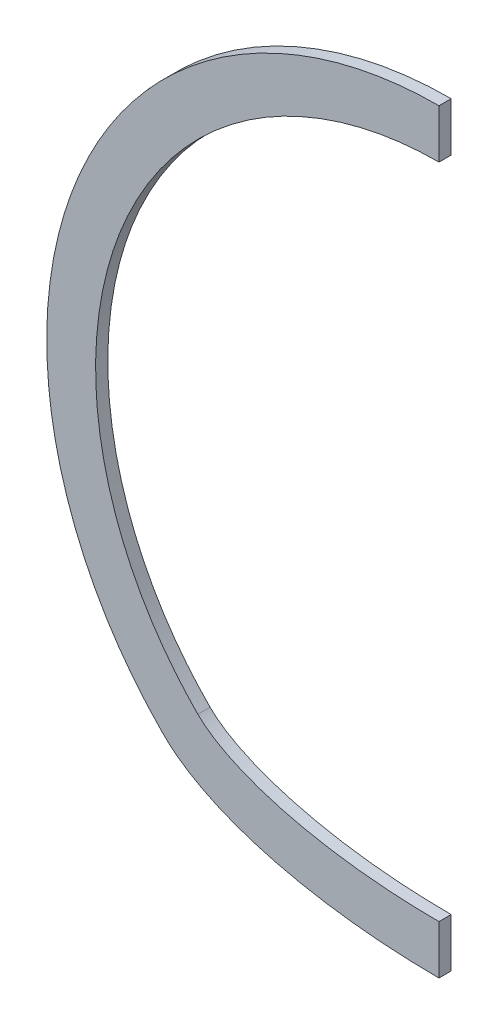
SolidWorks part; units mm, degrees
material "Balsa"
ref_plane "Front Plane" through (0, 0, 0) normal (0, 0, 1) x (1, 0, 0)
ref_plane "Top Plane" through (0, 0, 0) normal (0, 1, 0) x (1, 0, 0)
ref_plane "Right Plane" through (0, 0, 0) normal (1, 0, 0) x (0, 0, -1)
sketch "Sketch2" plane through (0, 0, 0) normal (0, 0, 1) x (1, 0, 0)
  spline S0 degree 3 poles (2568.0953, -4090.4659) (-4057.024, 3451.1389) (4945.1528, -1980.2124) (-4825.8731, 402.3844) knots -545.10296 -545.10296 -545.10296 -545.10296 547.49362 547.49362 547.49362 547.49362 only from (49.5009, 91.348) to (50.6103, 90.7129)
  spline S1 degree 3 poles (3341.4723, -3725.6669) (-100.6677, -22.1088) (-50.1916, -95.8099) (-74.4696, -70.0026) (-75.8372, -68.488) (-77.1861, -66.9319) (-78.5157, -65.3347) (-79.8244, -63.6962) (-81.5476, -61.4464) (-83.6416, -58.5297) (-85.6296, -55.5014) (-87.1622, -52.9973) (-88.2859, -51.0701) (-90.1147, -47.7724) (-92.5499, -42.8914) (-95.3516, -36.1752) (-97.8068, -28.8548) (-99.4166, -22.4927) (-100.4844, -16.9735) (-101.2174, -12.1158) (-101.8059, -6.1085) (-102.0556, 1.0556) (-101.6376, 11.9166) (-99.5817, 24.7034) (-94.9478, 39.4776) (-88.6565, 52.7081) (-80.0434, 65.5541) (-69.8712, 76.7554) (-58.637, 85.9148) (-47.202, 92.899) (-35.7905, 98.0522) (-24.0008, 101.7167) (-12.0295, 103.8942) (-3.6569, 104.3953) (0.9911, 104.3723) (2.6447, 104.3478) (5.2959, 104.2559) (8.9441, 104.0024) (12.9235, 103.5662) (16.8979, 102.9692) (20.8607, 102.2106) (24.805, 101.2899) (28.7242, 100.207) (32.6113, 98.9619) (36.4593, 97.5551) (39.9429, 96.1186) (42.4433, 94.9816) (43.9946, 94.2376) (44.9225, 93.7809) (45.8466, 93.3143) (46.7667, 92.8378) (47.6827, 92.3514) (70.4007, 80.003) (151.5153, 23.3747) (-4363.3748, 2440.7113) knots -0.313173 -0.313173 -0.313173 -0.313173 0.006795 0.013654 0.020575 0.02756 0.034609 0.041722 0.048899 0.063446 0.078252 0.085753 0.09332 0.100952 0.124124 0.148785 0.174948 0.202627 0.215494 0.232144 0.2526 0.276886 0.305032 0.363116 0.408011 0.462235 0.511576 0.564908 0.615598 0.658549 0.700916 0.742691 0.78387 0.82445 0.827809 0.831171 0.841279 0.854802 0.868378 0.882008 0.895692 0.909428 0.923217 0.93706 0.950955 0.964902 0.975398 0.978902 0.982411 0.985922 0.989437 0.992954 0.996476 1.262403 1.262403 1.262403 1.262403 only from (-71.6774, -72.9104) to (49.5009, 91.348)
  spline S2 degree 3 poles (-71.6774, -72.9104) (-72.1092, -72.4767) (-72.9729, -71.5936) (-74.4696, -70.0026) (-75.8372, -68.488) (-77.1861, -66.9319) (-78.5157, -65.3347) (-79.8244, -63.6962) (-81.5476, -61.4464) (-83.6416, -58.5297) (-85.6296, -55.5014) (-87.1622, -52.9973) (-88.2859, -51.0701) (-90.1147, -47.7724) (-92.5499, -42.8914) (-95.3516, -36.1752) (-97.8068, -28.8548) (-99.4166, -22.4927) (-100.4844, -16.9735) (-101.2174, -12.1158) (-101.8059, -6.1085) (-102.0556, 1.0556) (-101.6376, 11.9166) (-99.5817, 24.7034) (-94.9478, 39.4776) (-88.6565, 52.7081) (-80.0434, 65.5541) (-69.8712, 76.7554) (-58.637, 85.9148) (-47.202, 92.899) (-35.7905, 98.0522) (-24.0008, 101.7167) (-12.0295, 103.8942) (-3.6569, 104.3953) (0.9911, 104.3723) (2.6447, 104.3478) (5.2959, 104.2559) (8.9441, 104.0024) (12.9235, 103.5662) (16.8979, 102.9692) (20.8607, 102.2106) (24.805, 101.2899) (28.7242, 100.207) (32.6113, 98.9619) (36.4593, 97.5551) (39.9429, 96.1186) (42.4433, 94.9816) (43.9946, 94.2376) (44.9225, 93.7809) (45.8466, 93.3143) (46.7667, 92.8378) (47.6827, 92.3514) (48.5618, 91.8735) (49.1883, 91.5244) (49.5009, 91.348) knots 0 0 0 0 0.006795 0.013654 0.020575 0.02756 0.034609 0.041722 0.048899 0.063446 0.078252 0.085753 0.09332 0.100952 0.124124 0.148785 0.174948 0.202627 0.215494 0.232144 0.2526 0.276886 0.305032 0.363116 0.408011 0.462235 0.511576 0.564908 0.615598 0.658549 0.700916 0.742691 0.78387 0.82445 0.827809 0.831171 0.841279 0.854802 0.868378 0.882008 0.895692 0.909428 0.923217 0.93706 0.950955 0.964902 0.975398 0.978902 0.982411 0.985922 0.989437 0.992954 0.996476 1 1 1 1
  spline S3 degree 3 poles (49.5009, 91.348) (49.872, 91.1385) (50.2418, 90.9268) (50.6103, 90.7129) knots 0 0 0 0 1 1 1 1
  spline S4 degree 3 poles (-4193.7763, 2732.8048) (81.5381, 53.7028) (23.1515, 107.7521) (53.9325, 88.7036) (55.5798, 87.6387) (57.2181, 86.5331) (58.847, 85.3874) (60.4652, 84.2011) (62.6149, 82.559) (65.2687, 80.4032) (68.3802, 77.661) (71.4204, 74.7537) (74.3792, 71.6812) (77.2464, 68.4441) (79.5428, 65.6199) (81.3243, 63.2803) (82.6352, 61.4798) (83.9151, 59.6395) (85.6826, 56.9767) (87.8969, 53.3695) (90.4626, 48.6769) (92.8892, 43.6261) (95.1327, 38.2157) (97.1465, 32.4482) (98.8821, 26.3306) (100.2892, 19.8751) (101.2586, 13.4739) (101.8173, 7.2467) (102.0152, 1.305) (101.8786, -4.6242) (101.3926, -10.7347) (100.5371, -16.8676) (99.3294, -22.8638) (97.8936, -28.3722) (96.657, -32.2698) (95.7856, -34.7444) (95.046, -36.7643) (93.9532, -39.5358) (92.4358, -43.007) (90.8217, -46.3649) (89.1186, -49.6082) (87.3342, -52.7363) (85.4757, -55.7486) (83.5505, -58.6453) (81.5655, -61.4266) (79.3077, -64.3807) (77.437, -66.6472) (76.0073, -68.2889) (75.2951, -69.0897) (74.579, -69.8782) (73.8594, -70.6545) (73.1363, -71.4184) (59.0939, -85.9325) (120.7935, -16.6257) (-3396.6628, -3673.2191) knots -0.504739 -0.504739 -0.504739 -0.504739 0.010157 0.020393 0.030709 0.041103 0.051576 0.062128 0.072758 0.094254 0.116062 0.138181 0.16061 0.183347 0.206391 0.218027 0.22974 0.241529 0.253393 0.280162 0.30828 0.337739 0.36853 0.400644 0.434071 0.4688 0.504821 0.536145 0.567394 0.59857 0.62967 0.664059 0.696204 0.726123 0.75383 0.760691 0.767516 0.787768 0.807688 0.827278 0.84654 0.865477 0.884089 0.902378 0.920346 0.937994 0.961032 0.966703 0.97234 0.977942 0.983508 0.98904 0.994538 1.266327 1.266327 1.266327 1.266327 only from (50.6103, 90.7129) to (71.6784, -72.9104)
  spline S5 degree 3 poles (50.6103, 90.7129) (51.1284, 90.4118) (52.1672, 89.796) (53.9325, 88.7036) (55.5798, 87.6387) (57.2181, 86.5331) (58.847, 85.3874) (60.4652, 84.2011) (62.6149, 82.559) (65.2687, 80.4032) (68.3802, 77.661) (71.4204, 74.7537) (74.3792, 71.6812) (77.2464, 68.4441) (79.5428, 65.6199) (81.3243, 63.2803) (82.6352, 61.4798) (83.9151, 59.6395) (85.6826, 56.9767) (87.8969, 53.3695) (90.4626, 48.6769) (92.8892, 43.6261) (95.1327, 38.2157) (97.1465, 32.4482) (98.8821, 26.3306) (100.2892, 19.8751) (101.2586, 13.4739) (101.8173, 7.2467) (102.0152, 1.305) (101.8786, -4.6242) (101.3926, -10.7347) (100.5371, -16.8676) (99.3294, -22.8638) (97.8936, -28.3722) (96.657, -32.2698) (95.7856, -34.7444) (95.046, -36.7643) (93.9532, -39.5358) (92.4358, -43.007) (90.8217, -46.3649) (89.1186, -49.6082) (87.3342, -52.7363) (85.4757, -55.7486) (83.5505, -58.6453) (81.5655, -61.4266) (79.3077, -64.3807) (77.437, -66.6472) (76.0073, -68.2889) (75.2951, -69.0897) (74.579, -69.8782) (73.8594, -70.6545) (73.1363, -71.4184) (72.3175, -72.2647) (71.8912, -72.6967) (71.6784, -72.9104) knots 0 0 0 0 0.010157 0.020393 0.030709 0.041103 0.051576 0.062128 0.072758 0.094254 0.116062 0.138181 0.16061 0.183347 0.206391 0.218027 0.22974 0.241529 0.253393 0.280162 0.30828 0.337739 0.36853 0.400644 0.434071 0.4688 0.504821 0.536145 0.567394 0.59857 0.62967 0.664059 0.696204 0.726123 0.75383 0.760691 0.767516 0.787768 0.807688 0.827278 0.84654 0.865477 0.884089 0.902378 0.920346 0.937994 0.961032 0.966703 0.97234 0.977942 0.983508 0.98904 0.994538 1 1 1 1
  spline S6 degree 3 poles (-4835.9061, 806.008) (5645.7753, -391.3089) (-5645.7177, -391.3145) (4835.7602, 805.9912) knots -2.930767 -2.930767 -2.930767 -2.930767 3.930735 3.930735 3.930735 3.930735 weights 1 1 1 1 only from (71.6784, -72.9104) to (-71.6774, -72.9104)
  spline S7 degree 3 poles (71.6784, -72.9104) (46.3599, -98.3417) (-46.3589, -98.3417) (-71.6774, -72.9104) knots 0 0 0 0 1 1 1 1 weights 1 1 1 1
  spline S8 degree 1 poles (-62.6772, -63.9502) (43.2582, 80.2883) knots 0 0 1 1 construction
  spline S9 degree 1 poles (43.2582, 80.2883) (44.2327, 79.7303) knots 0 0 1 1 construction
  spline S10 degree 1 poles (44.2327, 79.7303) (62.6782, -63.9502) knots 0 0 1 1 construction
  spline S11 degree 1 poles (62.6782, -63.9502) (-62.6772, -63.9502) knots 0 0 1 1 construction
  spline S12 degree 3 poles (-62.6772, -63.9502) (-62.8955, -63.7309) (-63.3217, -63.2983) (-64.0021, -62.5921) (-64.7538, -61.7946) (-65.7039, -60.7646) (-66.8046, -59.5274) (-68.5568, -57.4681) (-70.6482, -54.8355) (-73.8114, -50.469) (-77.3945, -44.7561) (-82.3029, -35.1354) (-86.8108, -22.36) (-90.3543, -0.9674) (-87.6499, 26.3501) (-73.3334, 55.9721) (-49.624, 78.7088) (-24.4872, 89.3835) (-3.091, 92.1159) (13.039, 91.1975) (26.1203, 87.9966) (34.8794, 84.5248) (39.1021, 82.5104) (41.2143, 81.4108) (42.347, 80.7976) (42.9592, 80.4569) (43.2582, 80.2883) knots 0 0 0 0 0.003906 0.007812 0.011719 0.015625 0.023437 0.03125 0.046875 0.062499 0.093749 0.124999 0.187498 0.249998 0.374997 0.499996 0.624995 0.749994 0.812493 0.874993 0.937492 0.968742 0.984367 0.992179 0.996085 0.999992 0.999992 0.999992 0.999992
  spline S13 degree 3 poles (43.2582, 80.2883) (43.3397, 80.2423) (43.5025, 80.15) (43.7464, 80.0108) (43.9898, 79.871) (44.1518, 79.7773) (44.2327, 79.7303) knots 0.002022 0.002022 0.002022 0.002022 0.251014 0.500005 0.748996 0.997987 0.997987 0.997987 0.997987
  spline S14 degree 3 poles (44.2327, 79.7303) (44.5844, 79.526) (45.2596, 79.1276) (46.4154, 78.4223) (47.5738, 77.6928) (49.0079, 76.7584) (50.8048, 75.5306) (53.6072, 73.4932) (57.0034, 70.7903) (64.7641, 63.8421) (74.8536, 51.7693) (84.3118, 33.0007) (89.3026, 12.5818) (89.5941, -8.4639) (85.1673, -29.0225) (78.4712, -43.2887) (72.7378, -52.0045) (70.1455, -55.4923) (67.9548, -58.1887) (66.5372, -59.8344) (65.3768, -61.1241) (64.6361, -61.9238) (64.0489, -62.544) (63.5408, -63.0721) (63.0657, -63.5594) (62.8132, -63.8146) (62.6782, -63.9502) knots 0.000015 0.000015 0.000015 0.000015 0.007827 0.015639 0.023452 0.031264 0.046889 0.062514 0.093763 0.125013 0.250011 0.375009 0.500007 0.625005 0.750004 0.875002 0.906251 0.937501 0.953126 0.96875 0.976563 0.984375 0.988281 0.992188 0.996094 1 1 1 1
  spline S15 degree 3 poles (62.6782, -63.9502) (62.4421, -64.1873) (61.9735, -64.6322) (60.8483, -65.5949) (59.1789, -66.8259) (56.7375, -68.3252) (52.9423, -70.2888) (47.261, -72.5995) (39.2215, -74.978) (30.229, -76.8801) (17.3048, -78.7217) (0.0005, -79.6587) (-17.3038, -78.7217) (-30.228, -76.8801) (-39.2204, -74.978) (-47.2599, -72.5995) (-52.9413, -70.2888) (-56.7364, -68.3252) (-59.1779, -66.8259) (-60.8473, -65.5949) (-61.9724, -64.6322) (-62.4411, -64.1873) (-62.6772, -63.9502) knots 0 0 0 0 0.015625 0.03125 0.0625 0.09375 0.125 0.1875 0.25 0.3125 0.375 0.5 0.625 0.6875 0.75 0.8125 0.875 0.90625 0.9375 0.96875 0.984375 1 1 1 1
  dimension "D1" = 12.7
extrude "Boss-Extrude1" add sketch "Sketch2" against normal blind 3.175
sketch "Sketch3" plane through (0, 0, 0) normal (1, 0, 0) x (0, 0, -1)
  line L1 (-61.0107, 158.0584) -> (68.3789, 158.0584)
  line L2 (-61.0107, 158.0584) -> (-61.0107, -136.6623)
  line L3 (-61.0107, -136.6623) -> (68.3789, -136.6623)
  line L4 (68.3789, 158.0584) -> (68.3789, -136.6623)
extrude "Cut-Extrude1" cut sketch "Sketch3" along normal through all
